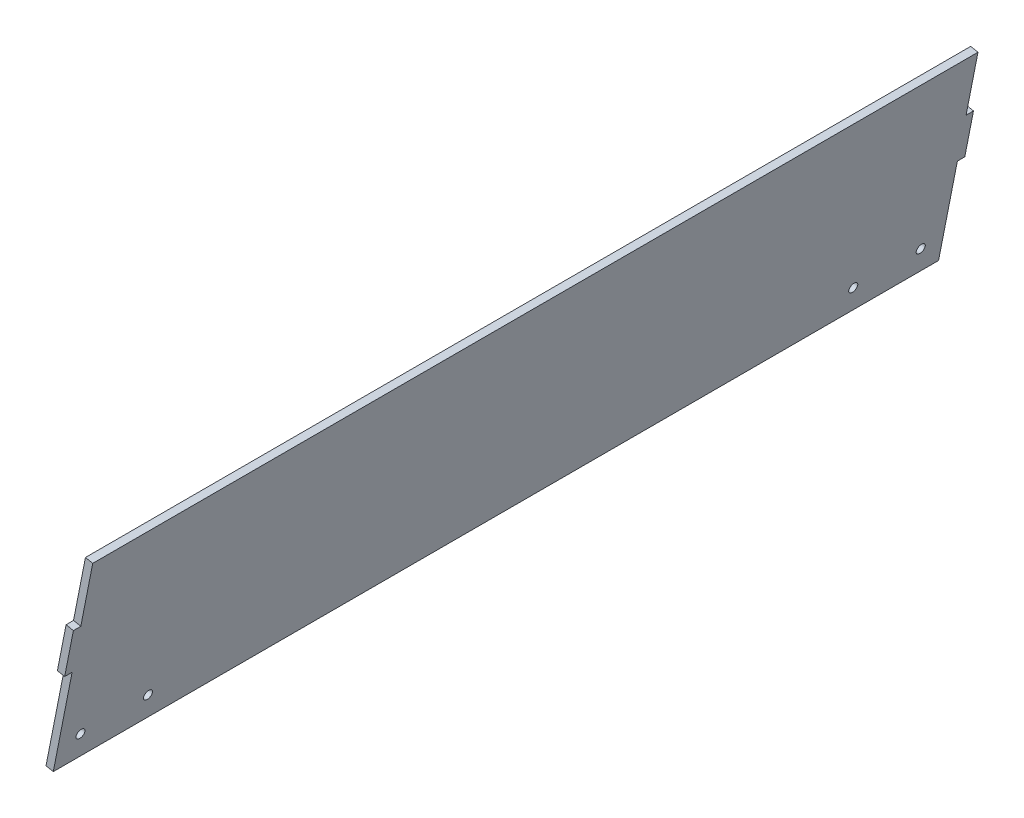
SolidWorks part; units mm, degrees
material "Balsa"
ref_plane "Front Plane" through (0, 0, 0) normal (0, 0, 1) x (1, 0, 0)
ref_plane "Top Plane" through (0, 0, 0) normal (0, 1, 0) x (1, 0, 0)
ref_plane "Right Plane" through (0, 0, 0) normal (1, 0, 0) x (0, 0, -1)
sketch "Sketch1" plane through (0, 0, 0) normal (0, 0, 1) x (1, 0, 0)
  line L0 (24.224, -184.5309) -> (41.7504, -95.5989)
  line L1 (74.6326, -84.2378) -> (-36.1779, -321.8717) construction
  line L2 (24.224, -184.5309) -> (27.4617, -185.169)
  line L3 (27.4617, -185.169) -> (44.9881, -96.237)
  line L4 (44.9881, -96.237) -> (41.7504, -95.5989)
  circle A1 centre (53.023, -69.9683) radius 17.5 construction
  dimension "D1" = 25
  dimension "D2" = 28
  dimension "D3" = 3.3
extrude "Boss-Extrude1" add sketch "Sketch1" along normal up to surface (393.4 mm away)
sketch "Sketch2" plane through (58.3254, -11.4945, 0) normal (-0.9811, 0.1934, 0) x (0, 0, 1)
  circle A0 centre (383.4, -165.6055) radius 2
  circle A1 centre (353.4, -165.6055) radius 2
  circle A2 centre (40, -165.6055) radius 2
  circle A3 centre (10, -165.6055) radius 2
  dimension "D1" = 4
  dimension "D2" = 4
  dimension "D3" = 4
  dimension "D4" = 4
extrude "Cut-Extrude1" cut sketch "Sketch2" against normal blind 4
sketch "Sketch4" plane through (0, 0, 0) normal (0, 0, -1) x (-1, 0, 0)
  line L0 (-32.5866, -142.0979) -> (-35.8243, -142.7359)
  line L1 (-32.5866, -142.0979) -> (-36.4537, -122.4753)
  line L2 (-35.8243, -142.7359) -> (-39.6914, -123.1134)
  line L3 (-36.4537, -122.4753) -> (-39.6914, -123.1134)
  line L4 (-27.4617, -185.169) -> (-44.9881, -96.237) construction
  line L5 (-36.4537, -122.4753) -> (-39.6914, -123.1134) construction
extrude "Boss-Extrude2" add sketch "Sketch4" along normal blind 3.3
extrude "Boss-Extrude3" add sketch "Sketch4<2>" against normal blind 3.3 from surface starting at face at (34.6061, -140.3839, 393.4)
sketch "Sketch4<2>" plane through (0, 0, 0) normal (0, 0, -1) x (-1, 0, 0) same geometry as "Sketch4"
